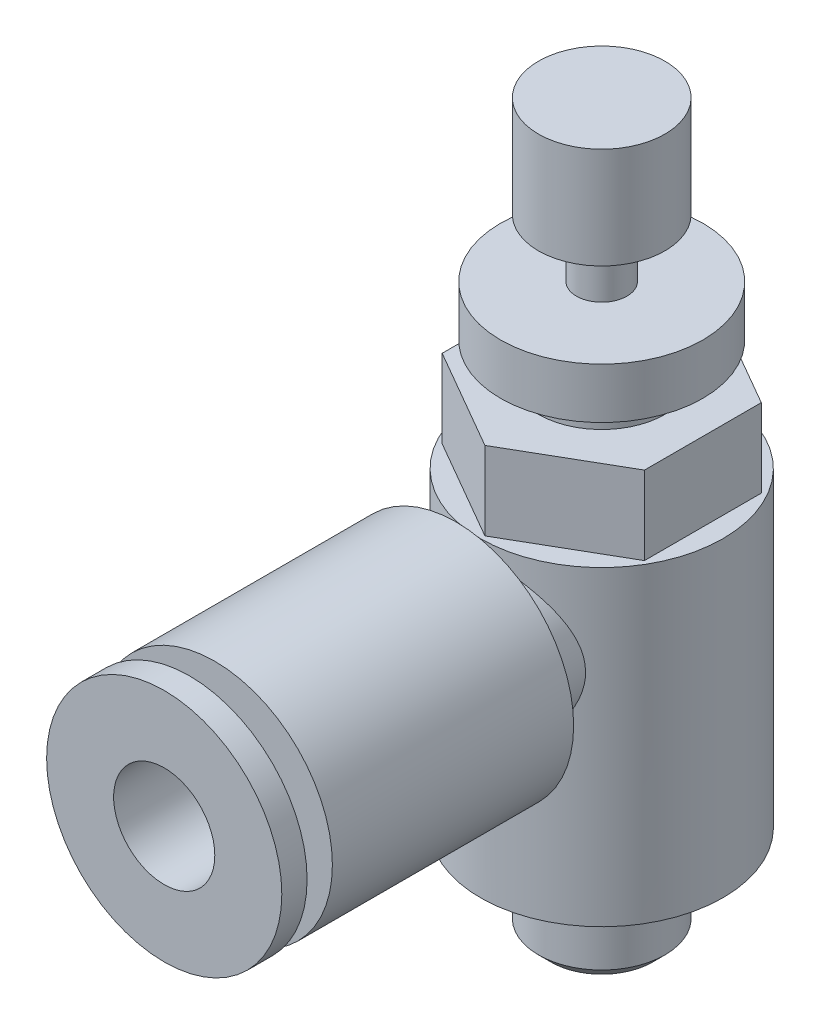
SolidWorks part; units mm, degrees
ref_plane "前视基准面" through (0, 0, 0) normal (0, 0, 1) x (1, 0, 0)
ref_plane "上视基准面" through (0, 0, 0) normal (0, 1, 0) x (1, 0, 0)
ref_plane "右视基准面" through (0, 0, 0) normal (1, 0, 0) x (0, 0, -1)
sketch "草图1" plane through (0, 0, 0) normal (0, 0, 1) x (1, 0, 0)
  line L0 (0, -3.6) -> (-2.0095, -3.6)
  line L1 (-2.0095, -3.6) -> (-2.5, -3.1095)
  line L2 (-2.5, -3.1095) -> (-2.5, -0.4905)
  line L3 (-2.5, -0.4905) -> (-2.0095, 0)
  line L4 (-2.0095, 0) -> (-4.8, 0)
  line L5 (-4.8, 0) -> (-4.8, 12.3)
  line L6 (-4.8, 12.3) -> (0, 12.3)
  line L7 (0, 12.3) -> (0, -3.6)
  line L8 (0, 12.3) -> (0, -3.6) construction
revolve "旋转1" add sketch "草图1" angle 360 about L8 reverse direction yes
cosmetic thread "装饰螺纹线1" parameters "D1"=3.6, "D2"=4.019
sketch "草图2" plane through (0, 0, 0) normal (1, 0, 0) x (0, 0, -1)
  line L0 (-17.3, 8.7) -> (-17.3, 13.35)
  line L1 (-17.3, 13.35) -> (-16.3, 13.35)
  line L2 (-16.3, 13.35) -> (-16.3, 11.7)
  line L3 (-16.3, 11.7) -> (-15.3, 11.7)
  line L4 (-15.3, 11.7) -> (-15.3, 13.35)
  line L5 (-15.3, 13.35) -> (-5.76, 13.35)
  line L6 (-5.76, 13.35) -> (-5.76, 11.76)
  line L7 (-5.76, 11.76) -> (0, 11.76)
  line L8 (0, 11.76) -> (0, 8.7)
  line L9 (0, 8.7) -> (-17.3, 8.7)
  line L10 (0, 8.7) -> (-17.3, 8.7) construction
revolve "旋转2" add sketch "草图2" angle 360 about L10 reverse direction yes
ref_plane "基准面1" through (0, 0, 17.3) normal (0, 0, 1) x (1, 0, 0)
sketch "草图3" plane through (0, 0, 17.3) normal (0, 0, 1) x (1, 0, 0)
  circle A0 centre (0, 8.7) radius 2
extrude "切除-拉伸1" cut sketch "草图3" against normal blind 12.7
ref_plane "基准面2" through (0, 0.5, 0) normal (0, 1, 0) x (-1, 0, 0)
sketch "草图4" plane through (0, 0, 0) normal (0, 0, 1) x (1, 0, 0)
  line L0 (0, 25) -> (2.5, 25)
  line L1 (2.5, 25) -> (2.5, 21)
  line L2 (2.5, 21) -> (1, 21)
  line L3 (1, 21) -> (1, 18.7)
  line L4 (1, 18.7) -> (4, 18.7)
  line L5 (4, 18.7) -> (4, 16.7)
  line L6 (4, 16.7) -> (2.5, 16.7)
  line L7 (2.5, 16.7) -> (2.5, 15.4)
  line L8 (2.5, 15.4) -> (4.8, 15.4)
  line L9 (4.8, 15.4) -> (4.8, 12.3)
  line L10 (4.8, 12.3) -> (0, 12.3)
  line L11 (0, 12.3) -> (0, 25)
  line L12 (0, 12.3) -> (0, 25) construction
revolve "旋转3" add sketch "草图4" angle 360 about L12 reverse direction yes
ref_plane "基准面3" through (0, 12.3, 0) normal (0, 1, 0) x (-1, 0, 0)
sketch "草图5" plane through (0, 12.3, 0) normal (0, 1, 0) x (-1, 0, 0)
  line L0 (4, -2.3094) -> (4, 2.3094)
  line L1 (4, 2.3094) -> (0, 4.6188)
  line L2 (0, 4.6188) -> (-4, 2.3094)
  line L3 (-4, 2.3094) -> (-4, -2.3094)
  line L4 (-4, -2.3094) -> (0, -4.6188)
  line L5 (0, -4.6188) -> (4, -2.3094)
  circle A0 centre (0, 0) radius 4.8
extrude "切除-拉伸2" cut sketch "草图5" along normal blind 3.1
